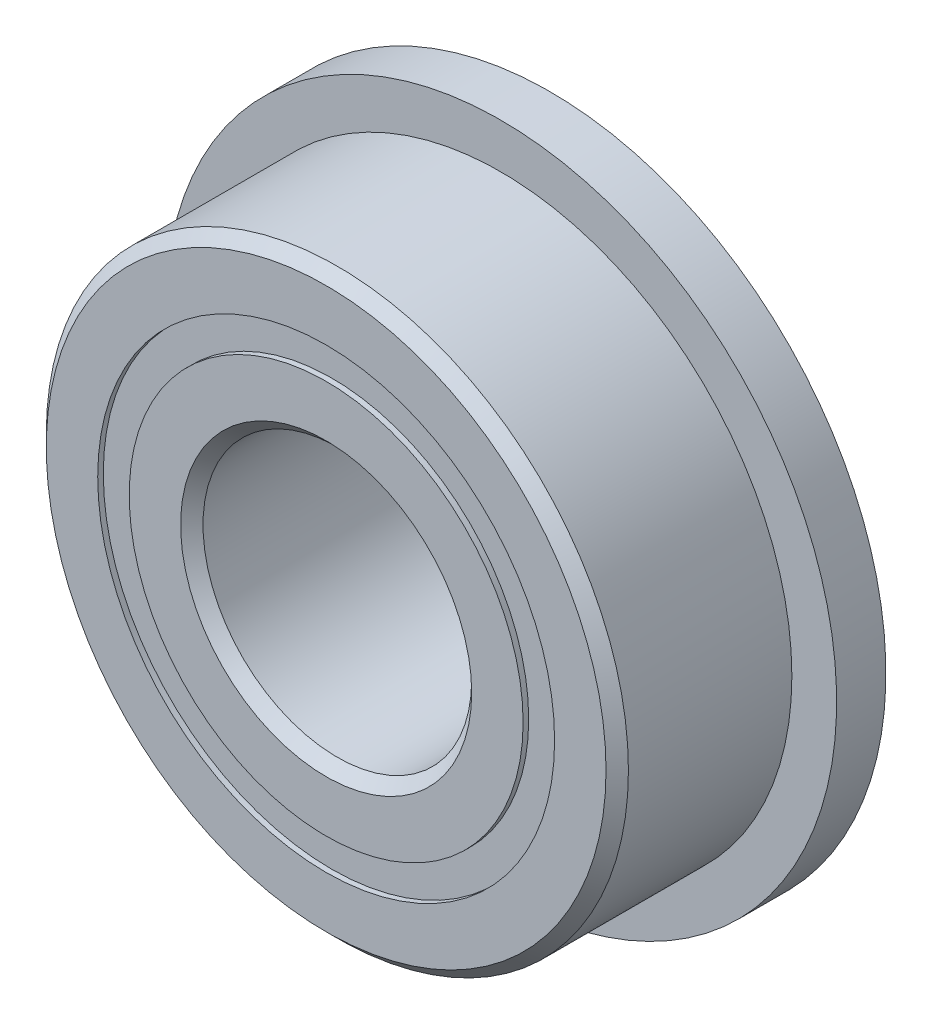
SolidWorks part; units mm, degrees
ref_plane "Front Plane" through (0, 0, 0) normal (0, 0, 1) x (1, 0, 0)
ref_plane "Top Plane" through (0, 0, 0) normal (0, 1, 0) x (1, 0, 0)
ref_plane "Right Plane" through (0, 0, 0) normal (1, 0, 0) x (0, 0, -1)
sketch "Sketch1" plane through (0, 0, 0) normal (1, 0, 0) x (0, 0, -1)
  line L0 (-2.5, 0) -> (2.5, 0) construction
  line L1 (0, 6.5) -> (0, -6.5) construction
  line L2 (2.25, 6.5) -> (-2.25, 6.5)
  line L3 (-2.25, 6.5) -> (-2.5, 6.25)
  line L4 (-2.5, 6.25) -> (-2.5, 5.1016)
  line L5 (-2.5, 5.1016) -> (-1.1111, 5.1016)
  line L6 (2.5, 5.1016) -> (1.1111, 5.1016)
  line L7 (2.5, 6.25) -> (2.5, 5.1016)
  line L8 (2.25, 6.5) -> (2.5, 6.25)
  line L9 (0, 6.5) -> (0, 4.75) construction
  line L10 (0, 4.75) -> (0, 3) construction
  arc A0 (-1.1111, 5.1016) -> (1.1111, 5.1016) centre (0, 4.75) cw
  point P14 (0, 3)
  dimension "D3" = 2.2222
  dimension "D1" = 45
  dimension "Width" = 5
  dimension "OD" = 13
  dimension "D2" = 0.25
  dimension "Shaft Dia" = 6
  dimension "D4" = 0.3516
revolve "Revolve1" add sketch "Sketch1" angle 360 about L0
sketch "Sketch3" plane through (0, 0, 0) normal (1, 0, 0) x (0, 0, -1)
  line L0 (-2.5, 4.3984) -> (-1.1111, 4.3984)
  line L1 (0, 6.5) -> (0, -6.5) construction
  line L2 (-2.5, 6.25) -> (-2.5, 5.1016) construction
  line L3 (-2.5, 4.3984) -> (-2.5, 3.25)
  line L4 (-2.25, 6.5) -> (-2.5, 6.25) construction
  line L5 (-2.5, 3.25) -> (-2.25, 3)
  line L6 (-2.25, 3) -> (2.25, 3)
  line L7 (2.25, 6.5) -> (2.25, -6.5) construction
  line L8 (2.25, 3) -> (2.5, 3.25)
  line L9 (2.5, -6.25) -> (2.5, 6.25) construction
  line L10 (2.5, 3.25) -> (2.5, 4.3984)
  line L11 (2.5, 4.3984) -> (1.1111, 4.3984)
  line L13 (2.25, 6.5) -> (2.5, 6.25) construction
  arc A0 (1.1111, 5.1016) -> (-1.1111, 5.1016) centre (0, 4.75) ccw construction
  arc A1 (1.1111, 4.3984) -> (-1.1111, 4.3984) centre (0, 4.75) cw
revolve "Revolve3" add sketch "Sketch3" angle 360 about L0
sketch "Sketch4" plane through (0, 0, 0) normal (1, 0, 0) x (0, 0, -1)
  line L0 (-1.1654, 4.75) -> (1.1654, 4.75)
  arc A2 (-1.1654, 4.75) -> (1.1654, 4.75) centre (0, 4.75) cw
  arc A3 (1.1111, 5.1016) -> (-1.1111, 5.1016) centre (0, 4.75) ccw construction
revolve "Revolve4" add sketch "Sketch4" angle 360 about L0
ref_axis "Axis1" through (0, 0, -2.5) along (0, 0, 1)
pattern_circular "CirPattern1" count 12 every 30 about axis through (0, 0, -2.5) along (0, 0, 1) of bodies 104
sketch "Sketch5" plane through (0, 0, 0) normal (1, 0, 0) x (0, 0, -1)
  line L0 (-2.5, 5.1016) -> (-1.1111, 5.1016) construction
  line L1 (-2.375, 5.1016) -> (-1.1654, 5.1016)
  line L2 (-2.375, 5.1016) -> (-2.375, 4.3984)
  line L3 (-2.375, 4.3984) -> (-1.1654, 4.3984)
  line L4 (-1.1654, 5.1016) -> (-1.1654, 4.3984)
  line L5 (-2.5, 4.3984) -> (-1.1111, 4.3984) construction
  line L6 (2.5, 5.1016) -> (1.1111, 5.1016) construction
  line L7 (2.375, 5.1016) -> (1.1654, 5.1016)
  line L8 (2.375, 5.1016) -> (2.375, 4.3984)
  line L9 (2.375, 4.3984) -> (1.1654, 4.3984)
  line L10 (1.1654, 5.1016) -> (1.1654, 4.3984)
  line L11 (2.5, 4.3984) -> (1.1111, 4.3984) construction
  line L12 (-2.25, 6.5) -> (-2.5, 6.25) construction
  point P18 (-2.375, 6.375)
revolve "Revolve5" add sketch "Sketch5" angle 360 about L0
sketch "Sketch6" plane through (0, 0, 0) normal (1, 0, 0) x (0, 0, -1)
  line L0 (2.5, 0) -> (-2.5, 0) construction
  line L1 (2.5, 5.1016) -> (1.4, 5.1016)
  line L2 (2.5, 5.1016) -> (2.5, 7.5)
  line L3 (2.5, 7.5) -> (1.4, 7.5)
  line L4 (1.4, 5.1016) -> (1.4, 7.5)
  dimension "Th" = 1.1
  dimension "Flange OD" = 15
revolve "Revolve6" add sketch "Sketch6" angle 360 about L0
equation "\"D2@Sketch1\" = \"Width@Sketch1\"*.05"
equation "\"D3@Sketch1\" = \"Width@Sketch1\"/2.25"
equation "\"D4@Sketch1\" = (((\"OD@Sketch1\"-\"Width@Sketch1\")/2)/3.25)/3.5"
equation "\"D2@CirPattern1\" = 360/\"Balls@CirPattern1\""
